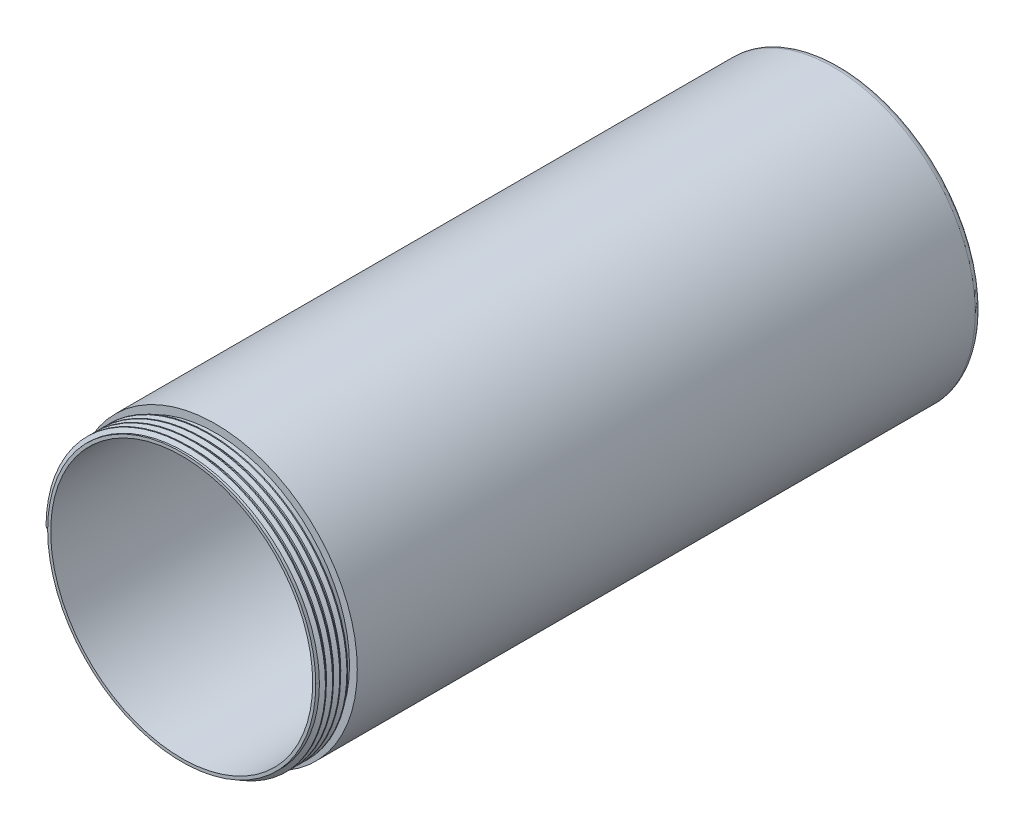
SolidWorks part; units mm, degrees
ref_plane "Front Plane" through (0, 0, 0) normal (0, 0, 1) x (1, 0, 0)
ref_plane "Top Plane" through (0, 0, 0) normal (0, 1, 0) x (1, 0, 0)
ref_plane "Right Plane" through (0, 0, 0) normal (1, 0, 0) x (0, 0, -1)
sketch "Sketch1" plane through (0, 0, 0) normal (0, 1, 0) x (1, 0, 0)
  circle A0 centre (0, 0) radius 42
  dimension "D1" = 84
extrude "Boss-Extrude1" add sketch "Sketch1" along normal blind 195 contours A0
sketch "Sketch2" plane through (0, 195, 0) normal (0, 1, 0) x (1, 0, 0)
  circle A0 centre (0, 0) radius 40
move or copy body "Body-Move/Copy1" bodies to move or copy 101 copy no translate (-42, 11.3402, 0)
move or copy body "Body-Move/Copy2" bodies to move or copy 104 copy no rotation origin (0, 108.8402, 0) rotation axis (1, 0, 0) rotation angle 90
move or copy body "Body-Move/Copy3" bodies to move or copy 105 copy no translate (-3.3007, -3.6422, -82.8031)
sketch "Sketch3" plane through (0, 0, 14.6969) normal (0, 0, 1) x (1, 0, 0)
  circle A2 centre (-45.3007, 105.198) radius 41
  circle A3 centre (-45.3007, 105.198) radius 41
  dimension "D1" = 1
fillet "Fillet1" radius 2 1 edges at (-45.3007, 63.198, -180.3031)
sketch "Sketch5" plane through (0, 0, 14.6969) normal (0, 0, 1) x (1, 0, 0)
  circle A2 centre (-45.3007, 105.198) radius 38.8
  circle A3 centre (-45.3007, 105.198) radius 38.8
  dimension "D1" = 3.2
extrude "Cut-Extrude1" cut sketch "Sketch5" against normal blind 190
sketch "Sketch6" plane through (0, 0, 14.6969) normal (0, 0, 1) x (1, 0, 0)
  circle A2 centre (-45.3007, 105.198) radius 40
  circle A3 centre (-45.3007, 105.198) radius 40
  dimension "D1" = 2
extrude "Cut-Extrude2" cut sketch "Sketch6" against normal blind 10 flip side to cut
sketch "Sketch7" plane through (0, 0, 14.6969) normal (0, 0, 1) x (1, 0, 0)
  circle A3 centre (-45.3007, 105.198) radius 40.3
  circle A4 centre (-45.3007, 105.198) radius 40.3
  dimension "D1" = 0.3
sketch "Sketch8" plane through (0, 0, 14.6969) normal (0, 0, 1) x (1, 0, 0)
  circle A2 centre (-45.3007, 105.198) radius 39.7
  circle A3 centre (-45.3007, 105.198) radius 39.7
  dimension "D1" = 0.3
extrude "Cut-Extrude5" cut sketch "Sketch8" against normal blind 10 flip side to cut
thread "Thread1" pitch 2.1167 method extrude profile "Thread Profile1" start angle 0, offset 0, length 8, pitch 2.1167, diameter 79.4
ref_plane "Plane1" through (-85.0007, 105.198, 14.6969) normal (0, -1, 0) x (-1, 0, 0)
sketch "Thread Profile1" plane through (-85.0007, 105.198, 14.6969) normal (0, -1, 0) x (-1, 0, 0)
  line L0 (0, 0) -> (0, 2.1167) construction
  line L1 (0, 0) -> (1.1457, 0.6615)
  line L2 (1.1457, 0.6615) -> (1.1457, 0.926)
  line L3 (1.1457, 0.926) -> (0, 1.5875)
  line L4 (1.1457, 0.7937) -> (0, 0.7937) construction
  line L11 (0, 0) -> (0, 1.5875)
  point P2 (0, 0)
  dimension "Pitch" = 2.1167
  dimension "Profile_Angle" = 60
  dimension "Profile_Land" = 0.2646
  dimension "Profile_Height" = 1.1457
